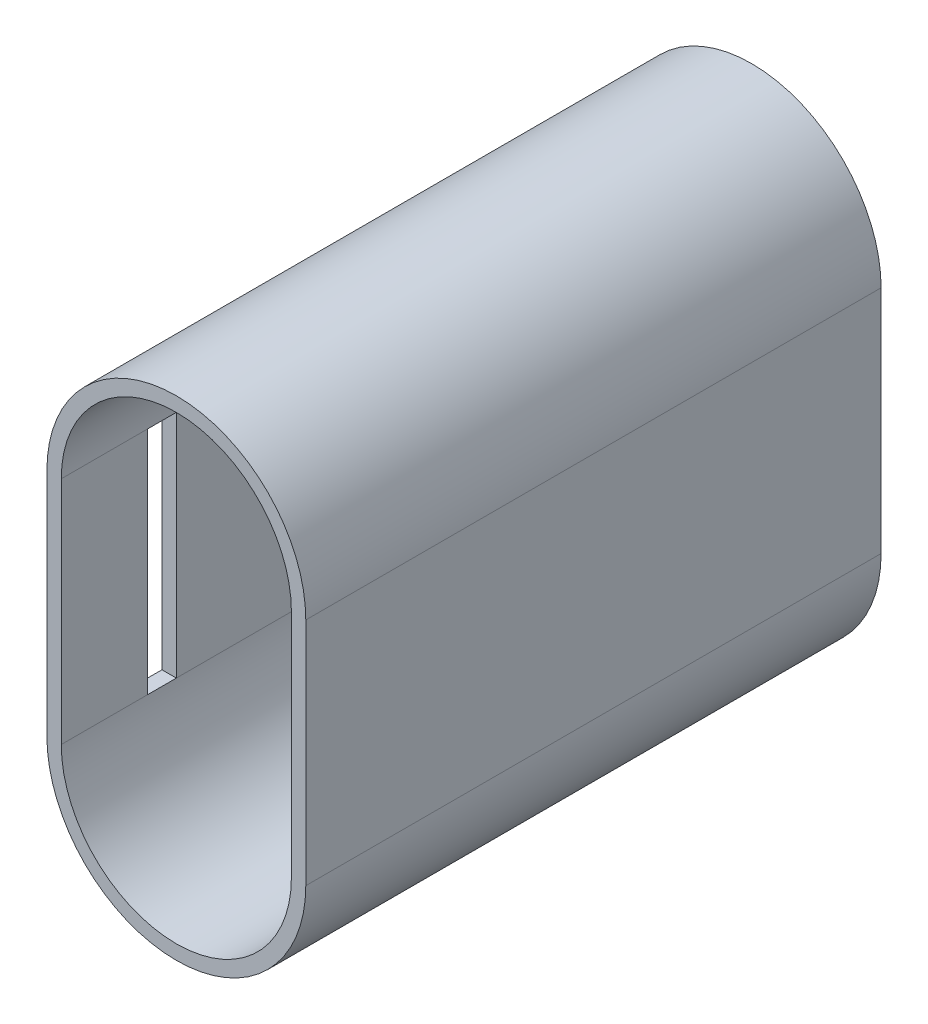
SolidWorks part; units mm, degrees
material "AISI 316 Нержавеющая сталь, лист (SS)"
ref_plane "Спереди" through (0, 0, 0) normal (0, 0, 1) x (1, 0, 0)
ref_plane "Сверху" through (0, 0, 0) normal (0, 1, 0) x (1, 0, 0)
ref_plane "Справа" through (0, 0, 0) normal (1, 0, 0) x (0, 0, -1)
other "Configuration Table"
sketch "Эскиз1" plane through (0, 0, 0) normal (0, 0, 1) x (1, 0, 0)
  line L0 (0, -40) -> (0, 40) construction
  line L1 (-45, -40) -> (-45, 40)
  line L2 (-40, -40) -> (-40, 40)
  line L3 (40, -40) -> (40, 40)
  line L4 (45, -40) -> (45, 40)
  arc A0 (-40, -40) -> (40, -40) centre (0, -40) ccw
  arc A1 (40, 40) -> (-40, 40) centre (0, 40) ccw
  arc A2 (45, 40) -> (-45, 40) centre (0, 40) ccw
  arc A3 (-45, -40) -> (45, -40) centre (0, -40) ccw
  point P3 (0, 80)
  point P4 (0, -80)
  point P5 (0, 0)
  dimension "D2" = 80
  dimension "D1" = 160
  dimension "D3" = 5
extrude "длина_камеры" add sketch "Эскиз1" along normal blind 200
sketch "Эскиз2" plane through (-45, 0, 0) normal (-1, 0, 0) x (0, 0, 1)
  line L0 (100, 40) -> (100, -40) construction
  line L1 (200, 40) -> (0, 40) construction
  line L2 (200, -40) -> (0, -40) construction
  line L4 (43, 40) -> (30, 40)
  line L5 (43, 40) -> (43, -40)
  line L6 (43, -40) -> (30, -40)
  line L7 (30, 40) -> (30, -40)
  line M6 (0, -40) -> (200, -40)
  line M8 (200, 40) -> (0, 40)
  dimension "D1" = 13
  dimension "D2" = 70
extrude "выпуск" cut sketch "Эскиз2" against normal up to surface (5 mm away) and the other way through all contours L7 L5 M8 M6 region at (-45, 0, 36.5) up to face at (-40, 0, 100)
sketch "Эскиз3" plane through (-45, 0, 0) normal (-1, 0, 0) x (0, 0, 1)
  line L0 (0, 40) -> (200, 40) construction
  line L1 (100, 40) -> (100, -40) construction
  line L2 (200, -40) -> (43, -40) construction
  line L4 (160, 40) -> (170, 40)
  line L5 (160, 40) -> (160, -40)
  line L6 (160, -40) -> (170, -40)
  line L7 (170, 40) -> (170, -40)
  line M6 (43, -40) -> (200, -40)
  line M8 (200, 40) -> (43, 40)
  dimension "D1" = 70
  dimension "D2" = 10
extrude "впуск" cut sketch "Эскиз3" along direction (1, 0, 0) on the side against the normal up to surface (5 mm away) contours L7 L5 M8 M6 region at (-45, 0, 165) up to face at (-40, 0, 121.5)
